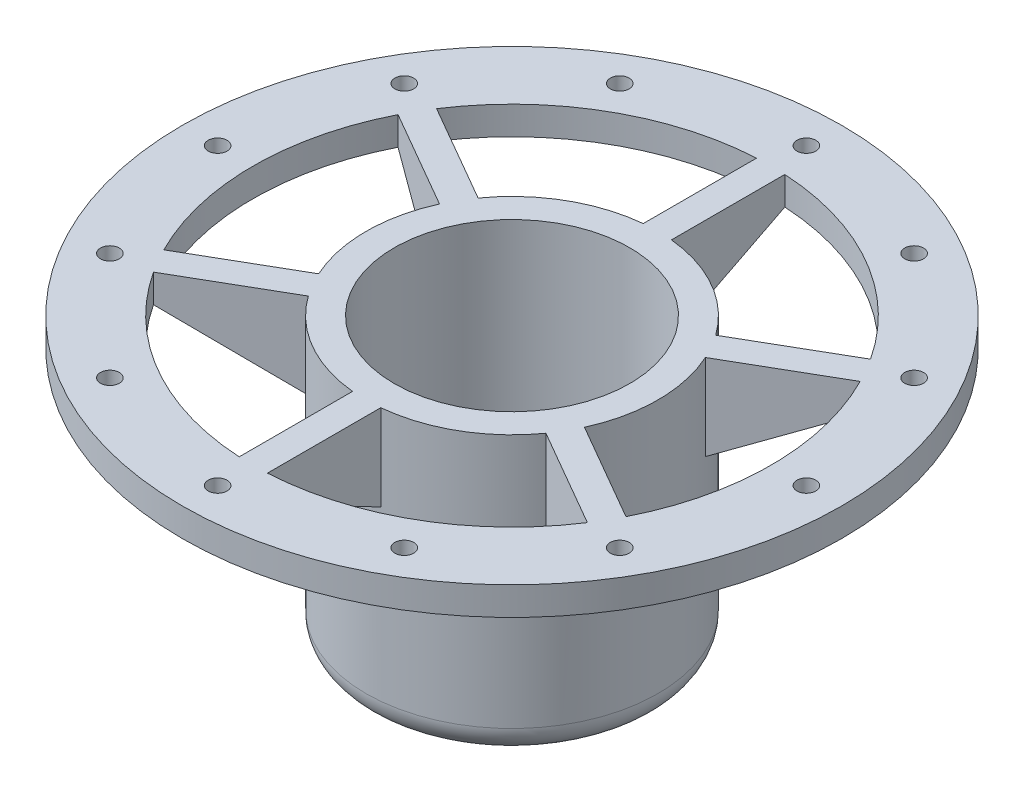
SolidWorks part; units mm, degrees
note: The reader was unsure of these and kept them because the rebuilt part matched: shared geometry of "Sketch2<3>".
ref_plane "Front Plane" through (0, 0, 0) normal (0, 0, 1) x (1, 0, 0)
ref_plane "Top Plane" through (0, 0, 0) normal (0, 1, 0) x (1, 0, 0)
ref_plane "Right Plane" through (0, 0, 0) normal (1, 0, 0) x (0, 0, -1)
sketch "Sketch1" plane through (0, 0, 0) normal (0, 1, 0) x (1, 0, 0)
  line L0 (-16, 0) -> (0, 0) construction
  line L1 (0, 0) -> (16, 0) construction
  circle A0 centre (0, 0) radius 25
  circle A1 centre (0, 0) radius 4
  circle A2 centre (16, 0) radius 3.3333
  circle A3 centre (-16, 0) radius 3
  dimension "D1" = 6
  dimension "D2" = 8
  dimension "D3" = 50
  dimension "D4" = 16
sketch "Sketch2" plane through (0, 0, 0) normal (0, 1, 0) x (1, 0, 0)
  circle A0 centre (0, 0) radius 31
  circle A1 centre (0, 0) radius 25
  circle A2 centre (16, 0) radius 3.3333
  circle A3 centre (-16, 0) radius 3
  circle A4 centre (0, 0) radius 4
  dimension "D1" = 6
extrude "Boss-Extrude1" add sketch "Sketch2" against normal blind 10 contours A0 A1 | A1 A4 A3 A2
extrude "Boss-Extrude2" add sketch "Sketch2<3>" along normal blind 50 contours A0 A1
sketch "Sketch2<3>" plane through (0, 0, 0) normal (0, 1, 0) x (1, 0, 0) same geometry as "Sketch2"
fillet "Fillet1" radius 6 1 edges at (0, -10, 31)
sketch "Sketch3" plane through (0, -10, 0) normal (0, -1, 0) x (1, 0, 0)
  circle A0 centre (16, 0) radius 7
  circle A1 centre (-16, 0) radius 7
  dimension "D1" = 14
extrude "Cut-Extrude1" cut sketch "Sketch3" against normal blind 3
sketch "Sketch4" plane through (0, 50, 0) normal (0, 1, 0) x (1, 0, 0)
  line L0 (0, -70) -> (0, 70) construction
  line L1 (2.9976, 30.8547) -> (2.9976, 54.9183)
  line L2 (-2.9976, 54.9183) -> (-2.9976, 30.8547)
  line L3 (0, 42.8865) -> (-2.9976, 42.8865) construction
  line L5 (2.9976, 42.8865) -> (0, 42.8865) construction
  line L7 (0, 31) -> (0, 55)
  circle A0 centre (0, 0) radius 55 construction
  circle A1 centre (0, 0) radius 70 construction
  arc A2 (0, 31) -> (2.9976, 30.8547) centre (0, 0) cw
  circle A4 centre (0, 0) radius 31 construction
  arc A5 (0, 31) -> (-2.9976, 30.8547) centre (0, 0) ccw
  arc A6 (0, 55) -> (-2.9976, 54.9183) centre (0, 0) ccw
  arc A7 (0, 55) -> (2.9976, 54.9183) centre (0, 0) cw
  point P7 (0, 0)
  point P13 (0, 0)
  circle M3 centre (0, 0) radius 31
  dimension "D1" = 140
  dimension "D2" = 15
extrude "Boss-Extrude3" add sketch "Sketch4" against normal blind 6 contours A7 L7 L1 M3 | L7 A6 L2 M3
sketch "Sketch5" plane through (0, 0, 0) normal (0, 0, 1) x (1, 0, 0)
  line L0 (0, 0) -> (0, 37.8207) construction
pattern_circular "CirPattern1" count 6 over 360 about axis through (0, 0, 0) along (0, 1, 0) of "Boss-Extrude3"
sketch "Sketch6" plane through (0, 0, 0) normal (0, 1, 0) x (1, 0, 0)
  circle A0 centre (0, 0) radius 55
  circle A1 centre (0, 0) radius 70
  circle A2 centre (0, 0) radius 55 construction
  circle A3 centre (0, 0) radius 70 construction
extrude "Boss-Extrude4" add sketch "Sketch6" along normal up to surface (6 mm away) from surface
chamfer "Chamfer1" distance 24 angle 27 6 edges at (0, 44, -31) (-26.8468, 44, 15.5) (-26.8468, 44, -15.5) (26.8468, 44, -15.5) (26.8468, 44, 15.5) (0, 44, 31)
sketch "Sketch7" plane through (0, 50, 0) normal (0, 1, 0) x (1, 0, 0)
  line L0 (0, -70) -> (0, 70) construction
  line L1 (0, -70) -> (0, -55)
  circle A0 centre (0, -62.5) radius 2
  circle A1 centre (0, 0) radius 55 construction
  circle A2 centre (0, 0) radius 70 construction
  point P4 (0, 0)
  point P9 (0, -62.5)
  dimension "D1" = 4
extrude "Cut-Extrude2" cut sketch "Sketch7" against normal blind 6 contours L1 A0 | L1 A0
pattern_circular "CirPattern2" count 12 over 360 about axis through (0, 0, 0) along (0, 1, 0) of "Cut-Extrude2"
